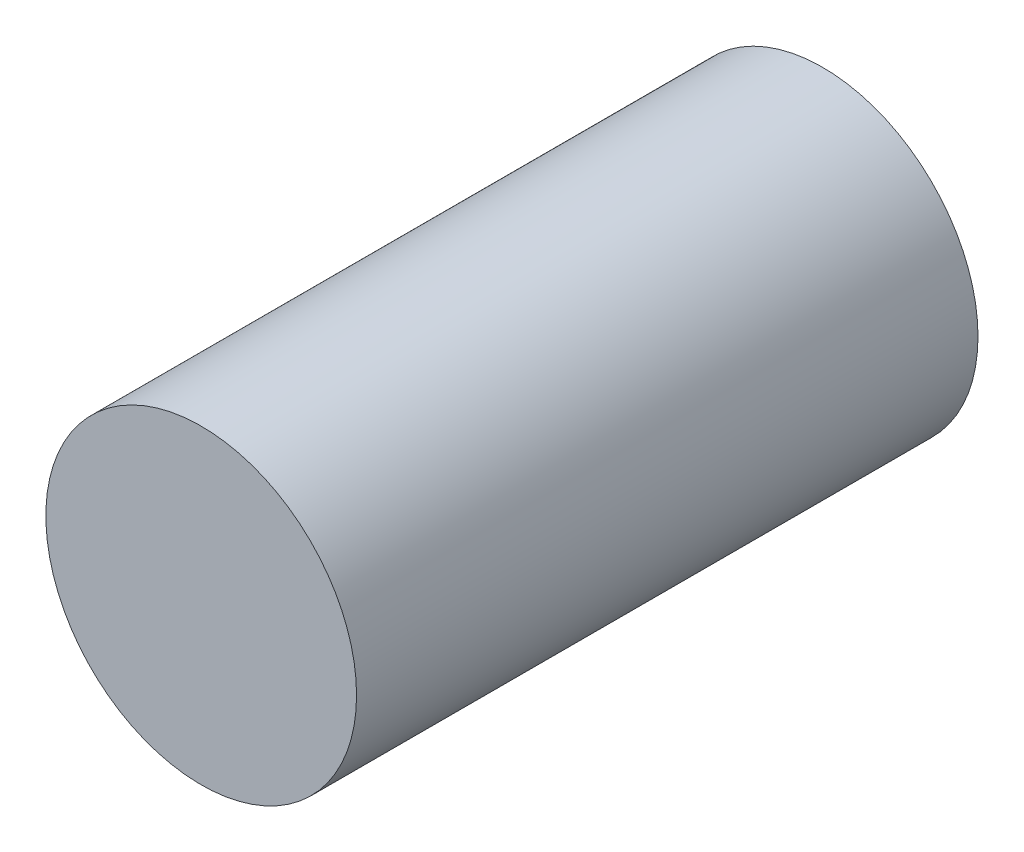
SolidWorks part; units mm, degrees
ref_plane "正面" through (0, 0, 0) normal (0, 0, 1) x (1, 0, 0)
ref_plane "平面" through (0, 0, 0) normal (0, 1, 0) x (1, 0, 0)
ref_plane "右側面" through (0, 0, 0) normal (1, 0, 0) x (0, 0, -1)
sketch "ｽｹｯﾁ1" plane through (0, 0, 0) normal (0, 0, 1) x (1, 0, 0)
  circle A0 centre (0, 0) radius 50
extrude "ﾎﾞｽ - 押し出し1" add sketch "ｽｹｯﾁ1" along normal blind 200
ref_axis "軸1" through (0, 0, 200) along (0, 0, -1)
